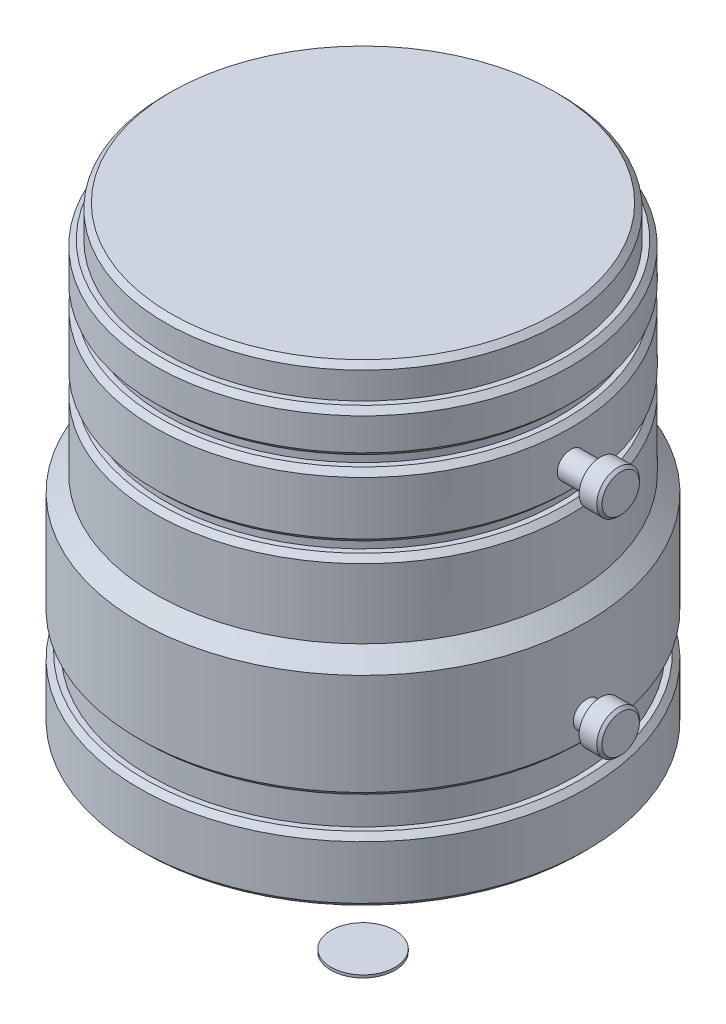
SolidWorks part; units mm, degrees
ref_plane "Front Plane" through (0, 0, 0) normal (0, 0, 1) x (1, 0, 0)
ref_plane "Top Plane" through (0, 0, 0) normal (0, 1, 0) x (1, 0, 0)
ref_plane "Right Plane" through (0, 0, 0) normal (1, 0, 0) x (0, 0, -1)
sketch "Sketch1" plane through (0, 0, 0) normal (0, 0, 1) x (1, 0, 0)
  line L0 (0, 0) -> (18.5, 0)
  line L1 (18.5, 0) -> (18.5, -3)
  line L2 (18.5, -3) -> (19.5, -3)
  line L3 (19.5, -3) -> (19.5, -7)
  line L4 (19.5, -7) -> (18.5, -7)
  line L5 (18.5, -7) -> (18.5, -8)
  line L6 (18.5, -8) -> (19.5, -8)
  line L7 (19.5, -8) -> (19.5, -14)
  line L8 (19.5, -14) -> (18.5, -14)
  line L9 (18.5, -14) -> (18.5, -15)
  line L10 (18.5, -15) -> (19.5, -15)
  line L11 (19.5, -15) -> (19.5, -22)
  line L12 (19.5, -22) -> (21, -22)
  line L13 (21, -22) -> (21, -33.5)
  line L14 (21, -33.5) -> (20, -33.5)
  line L15 (20, -33.5) -> (20, -36.5)
  line L16 (20, -36.5) -> (21, -36.5)
  line L17 (21, -36.5) -> (21, -42.5)
  line L18 (21, -42.5) -> (18, -42.5)
  line L19 (18, -42.5) -> (18, -43)
  line L20 (18, -43) -> (12.18, -43)
  line L21 (12.18, -43) -> (12.18, -43.75)
  line L22 (12.18, -43.75) -> (12.7, -43.75)
  line L23 (12.7, -43.75) -> (12.7, -47)
  line L24 (12.7, -47) -> (0, -47)
  line L25 (0, 0) -> (0, -47)
revolve "Lens Body" add sketch "Sketch1" angle 360 about L25
chamfer ".5mm Body Chamfers" distance 0.5 10 edges at (-18.5, 0, 0) (-19.5, -15, 0) (-19.5, -14, 0) (-19.5, -8, 0) (-19.5, -7, 0) (-19.5, -3, 0) (-21, -33.5, 0) (-21, -42.5, 0) (-21, -36.5, 0) (-18, -43, 0)
chamfer "1.5mm Body Chamfers" distance 1.5 angle 45 1 edges at (-21, -22, 0)
chamfer ".48mm x .28mm Body Chamfer 1" distance 0.28 distance2 0.48 1 edges at (-12.7, -43.75, 0) first distance on face at (-12.7, -43.75, 0)
chamfer ".48mm x .28mm Body Chamfer 2" distance 0.48 distance2 0.28 1 edges at (-12.7, -47, 0) first distance on face at (-12.7, -47, 0)
sketch "Sketch2" plane through (0, -47, 0) normal (0, -1, 0) x (1, 0, 0)
  circle A0 centre (0, 0) radius 9
extrude "Sensor Hole" cut sketch "Sketch2" against normal blind 10
sketch "Sketch7" plane through (0, 0, 0) normal (0, 0, 1) x (1, 0, 0)
  line L0 (20, -32.25) -> (22.25, -32.25)
  line L2 (22.25, -32.25) -> (22.25, -33)
  line L3 (22.25, -33) -> (24.15, -33)
  line L4 (24.15, -33) -> (24.15, -31)
  line L5 (20, -32.25) -> (20, -31)
  line L8 (24.15, -31) -> (20, -31)
revolve "Lower Knob" add sketch "Sketch7" angle 360 about L8
sketch "Sketch8" plane through (0, 0, 0) normal (0, 0, 1) x (1, 0, 0)
  line L1 (18.5, -12.75) -> (22.25, -12.75)
  line L2 (22.25, -12.75) -> (22.25, -13.5)
  line L3 (22.25, -13.5) -> (24.15, -13.5)
  line L4 (24.15, -13.5) -> (24.15, -11.5)
  line L5 (24.15, -11.5) -> (18.5, -11.5)
  line L6 (18.5, -11.5) -> (18.5, -12.75)
  point P0 (0, 0)
revolve "Upper Knob" add sketch "Sketch8" angle 360 about L5
chamfer ".25mm Upper Knob Chamfer" distance 0.25 1 edges at (24.15, -9.5, 0)
chamfer ".25mm Lower Knob Chamfer" distance 0.25 1 edges at (24.15, -31, -2)
ref_plane "Focal Plane" through (0, -60.78, 0) normal (0, 1, 0) x (1, 0, 0)
sketch "Sketch9" plane through (0, -60.78, 0) normal (0, 1, 0) x (1, 0, 0)
  circle A0 centre (0, 0) radius 3
extrude "Focal Point" add sketch "Sketch9" along normal blind 0.25 separate body
